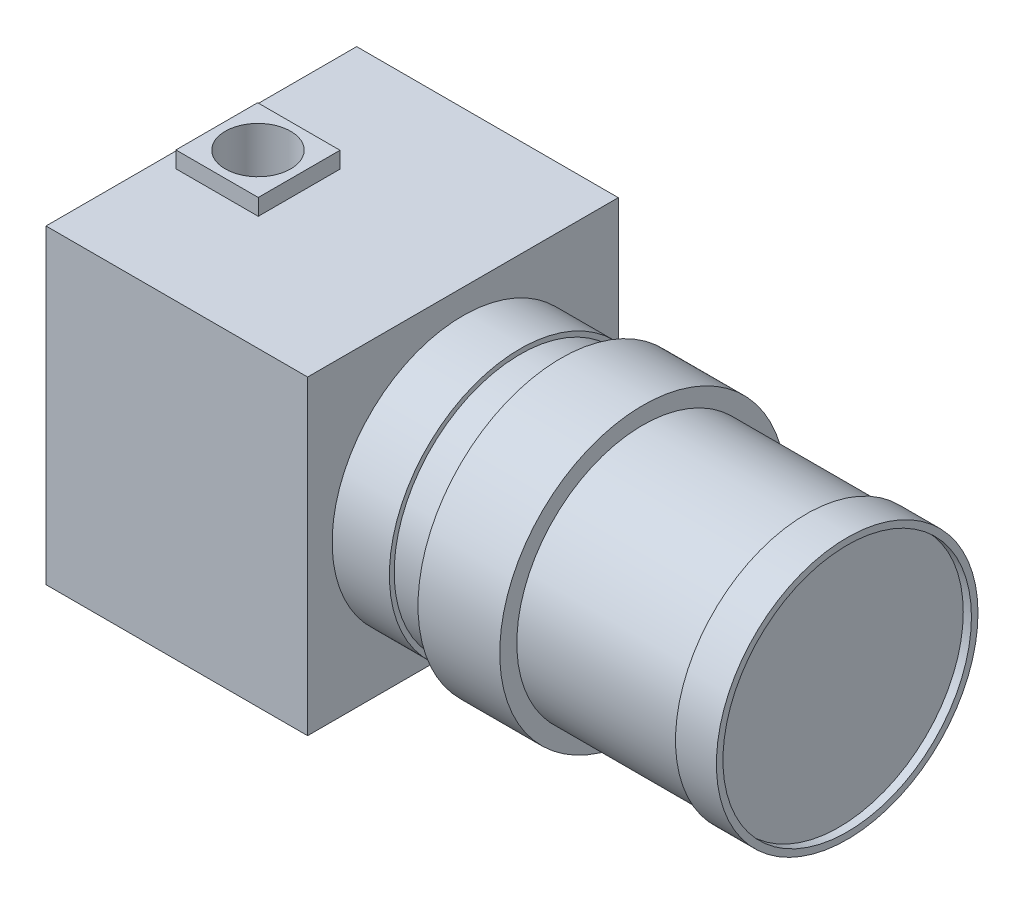
SolidWorks part; units mm, degrees
ref_plane "Front Plane" through (0, 0, 0) normal (0, 0, 1) x (1, 0, 0)
ref_plane "Top Plane" through (0, 0, 0) normal (0, 1, 0) x (1, 0, 0)
ref_plane "Right Plane" through (0, 0, 0) normal (1, 0, 0) x (0, 0, -1)
sketch "Sketch1" plane through (0, 0, 0) normal (1, 0, 0) x (0, 0, -1)
  line L1 (-19, 19) -> (19, 19)
  line L2 (-19, 19) -> (-19, -19)
  line L3 (-19, -19) -> (19, -19)
  line L4 (19, 19) -> (19, -19)
  line L5 (-19, 19) -> (19, -19) construction
  line L6 (-19, -19) -> (19, 19) construction
  point P0 (0, 0)
  dimension "D1" = 38
  dimension "D2" = 38
extrude "Boss-Extrude1" add sketch "Sketch1" along normal blind 32
sketch "Sketch2" plane through (32, 0, 0) normal (1, 0, 0) x (0, 0, -1)
  circle A0 centre (0, 0) radius 16
  dimension "D1" = 32
extrude "Boss-Extrude2" add sketch "Sketch2" along normal blind 47
sketch "Sketch3" plane through (0, 19, 0) normal (0, 1, 0) x (1, 0, 0)
  line L1 (1.8879, 5) -> (11.9619, 5)
  line L2 (1.8879, 5) -> (1.8879, -5)
  line L3 (1.8879, -5) -> (11.9619, -5)
  line L4 (11.9619, 5) -> (11.9619, -5)
  line L5 (1.8879, 5) -> (11.9619, -5) construction
  line L6 (1.8879, -5) -> (11.9619, 5) construction
  circle A1 centre (6.9249, 0) radius 4
  dimension "D1" = 8
extrude "Boss-Extrude3" add sketch "Sketch3" along normal blind 2
extrude "Cut-Extrude1" cut sketch "Sketch3<2>" against normal blind 5 contours A1 region at (6.9249, 19, 0)
sketch "Sketch3<2>" plane through (0, 19, 0) normal (0, 1, 0) x (1, 0, 0) same geometry as "Sketch3"
sketch "Sketch4" plane through (79, 0, 0) normal (1, 0, 0) x (0, 0, -1)
  circle A0 centre (0, 0) radius 16
  circle A1 centre (0, 0) radius 15.4129
  dimension "D1" = 32
  dimension "D2" = 30.8258
extrude "Cut-Extrude2" cut sketch "Sketch4" against normal blind 20 from offset 5 offset against normal yes
sketch "Sketch5" plane through (79, 0, 0) normal (1, 0, 0) x (0, 0, -1)
  circle A0 centre (0, 0) radius 16 construction
  circle A1 centre (0, 0) radius 16
  circle A2 centre (0, 0) radius 17.5
  dimension "D1" = 35
extrude "Boss-Extrude4" add sketch "Sketch5" against normal blind 10 from offset 25 offset against normal yes
extrude "Cut-Extrude3" cut sketch "Sketch4<2>" against normal blind 5 from offset 35 offset against normal yes
sketch "Sketch4<2>" plane through (79, 0, 0) normal (1, 0, 0) x (0, 0, -1) same geometry as "Sketch4"
sketch "Sketch6" plane through (79, 0, 0) normal (1, 0, 0) x (0, 0, -1)
  circle A0 centre (0, 0) radius 15.1977
  dimension "D1" = 30.3954
extrude "Cut-Extrude4" cut sketch "Sketch6" against normal blind 1
